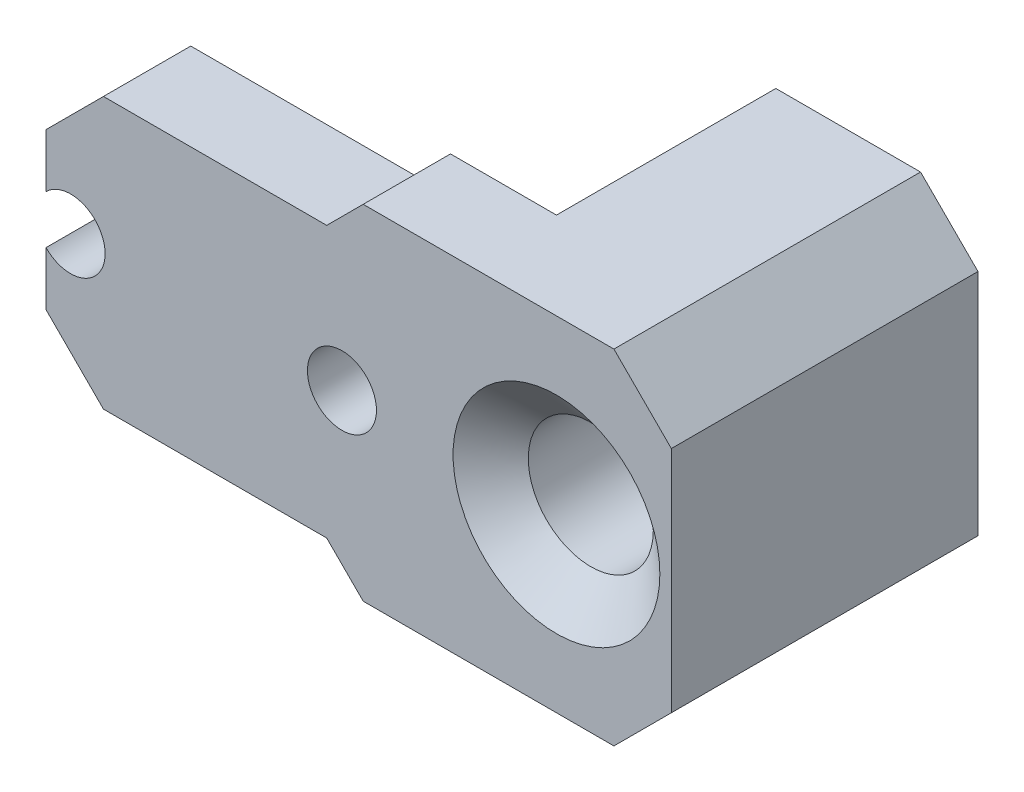
SolidWorks part; units mm, degrees
ref_plane "Front" through (0, 0, 0) normal (0, 0, 1) x (1, 0, 0)
ref_plane "Top" through (0, 0, 0) normal (0, 1, 0) x (1, 0, 0)
ref_plane "Right" through (0, 0, 0) normal (1, 0, 0) x (0, 0, -1)
sketch "Sketch1" plane through (0, 0, 0) normal (0, 0, 1) x (1, 0, 0)
  line L1 (6.254, 4.75) -> (12.604, 4.75)
  line L2 (6.254, 4.75) -> (6.254, -4.75)
  line L3 (6.254, -4.75) -> (12.604, -4.75)
  line L4 (12.604, 4.75) -> (12.604, -4.75)
  line L6 (6, -4.25) -> (6, -4) construction
  dimension "D1" = 0.254
  dimension "D2" = 6.35
extrude "Boss-Extrude1" add sketch "Sketch1" along normal up to surface (5.3 mm away)
sketch "Sketch2" plane through (0, 0, 5.3) normal (0, 0, 1) x (1, 0, 0)
  line L0 (12.604, 4.75) -> (12.604, -4.75) construction
  line L1 (12.604, -3.742) -> (-4.6794, -3.742)
  line L2 (12.604, -3.742) -> (12.604, 3.742)
  line L3 (12.604, 3.742) -> (-4.6794, 3.742)
  line L4 (-4.6794, -3.742) -> (-4.6794, 3.742)
  line L5 (1.4445, -4.25) -> (3.15, -4.25) construction
  line L6 (3.15, 4.25) -> (1.4445, 4.25) construction
  line L7 (-5.1874, -1.991) -> (-5.1874, -4.25) construction
  dimension "D1" = 0.508
  dimension "D2" = 0.508
  dimension "D3" = 0.508
extrude "Boss-Extrude2" add sketch "Sketch2" along normal blind 3.175
sketch "Sketch3" plane through (0, 0, 8.475) normal (0, 0, 1) x (1, 0, 0)
  circle A5 centre (-4, 0) radius 0.954
  circle A6 centre (-4, 0) radius 0.954
  circle A8 centre (3.5, 0) radius 0.954
  circle A9 centre (3.5, 0) radius 0.954
  dimension "D1" = 0.254
  dimension "D2" = 0.254
extrude "Cut-Extrude1" cut sketch "Sketch3" against normal through all
sketch "Sketch4" plane through (0, 0, 5.3) normal (0, 0, 1) x (1, 0, 0)
  line L0 (6.254, 3.742) -> (12.604, 3.742) construction
  line L1 (12.604, 3.742) -> (12.604, 4.75) construction
  line L2 (12.604, 4.75) -> (6.254, 4.75) construction
  line L3 (6.254, 4.75) -> (6.254, 3.742) construction
  line L4 (12.604, -3.742) -> (6.254, -3.742) construction
  line L5 (6.254, -3.742) -> (6.254, -4.75) construction
  line L6 (6.254, -4.75) -> (12.604, -4.75) construction
  line L7 (12.604, -4.75) -> (12.604, -3.742) construction
  line L8 (6.254, 3.742) -> (12.604, 3.742)
  line L9 (12.604, 3.742) -> (12.604, 4.75)
  line L10 (12.604, 4.75) -> (6.254, 4.75)
  line L11 (6.254, 4.75) -> (6.254, 3.742)
  line L12 (12.604, -3.742) -> (6.254, -3.742)
  line L13 (6.254, -3.742) -> (6.254, -4.75)
  line L14 (6.254, -4.75) -> (12.604, -4.75)
  line L15 (12.604, -4.75) -> (12.604, -3.742)
extrude "Boss-Extrude3" add sketch "Sketch4" along normal up to surface (3.175 mm away) up to face at (4.454, 0, 8.475)
chamfer "Chamfer1" distance 3.175 angle 45 2 edges at (6.254, 3.742, 6.8875) (6.254, -3.742, 6.8875)
chamfer "Chamfer2" distance 1.5875 angle 45 4 edges at (-4.6794, -3.742, 6.8875) (-4.6794, 3.742, 6.8875) (12.604, 4.75, 4.2375) (12.604, -4.75, 4.2375)
chamfer "Chamfer3" distance 0.762 angle 45 14 edges at (-3.046, 0, 5.3) (4.454, 0, 5.3) (6.254, 4.75, 2.65) (5.1705, 4.75, 5.3) (3.583, 4.246, 5.3) (-0.0065, 3.742, 5.3) (-3.8857, 2.9482, 5.3) (-4.6794, 1.4121, 5.3) (6.254, -4.75, 2.65) (5.1705, -4.75, 5.3) (3.583, -4.246, 5.3) (-0.0065, -3.742, 5.3) (-3.8857, -2.9482, 5.3) (-4.6794, -1.4121, 5.3)
hole_wizard "CSK for #4 Flat Head Machine Screw (100)1" positions "Sketch5" profile "Sketch6" countersink size "#4" standard "ANSI Inch" end condition through all
sketch "Sketch5" plane through (0, 0, 8.475) normal (0, 0, 1) x (1, 0, 0)
  line L0 (12.604, 0) -> (6.254, 0) construction
  line L1 (12.604, -3.1625) -> (12.604, 3.1625) construction
  line L3 (6.254, -3.988) -> (6.254, 3.988) construction
  point P0 (9.429, 0)
sketch "Sketch6" plane through (9.429, 0, 8.475) normal (1, 0, 0) x (0, -1, 0)
  line L0 (0, 0) -> (0, 8.475)
  line L1 (0, 8.475) -> (1.7272, 8.475)
  line L2 (1.7272, 8.475) -> (1.7272, 0.9484)
  line L3 (1.7272, 0.9484) -> (2.8575, 0)
  line L5 (2.8575, 0) -> (0, 0)
  line L6 (-1.7272, 0.9484) -> (-2.8575, 0) construction
  line L11 (0, -6.35) -> (0, 107.95) construction
  dimension "Thru Hole Dia." = 3.4544
  dimension "Thru Hole Depth" = 8.475
  dimension "Near C'Sink Dia." = 5.715
  dimension "Near C'Sink Angle" = 100
